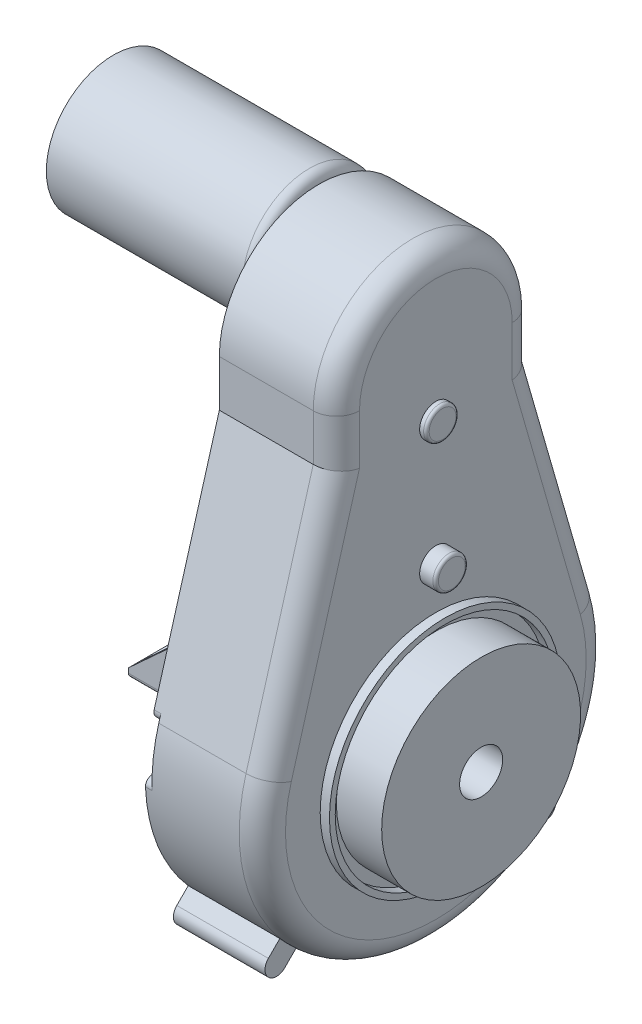
SolidWorks part; units mm, degrees
ref_plane "Front Plane" through (0, 0, 0) normal (0, 0, 1) x (1, 0, 0)
ref_plane "Top Plane" through (0, 0, 0) normal (0, 1, 0) x (1, 0, 0)
ref_plane "Right Plane" through (0, 0, 0) normal (1, 0, 0) x (0, 0, -1)
sketch "Sketch1" plane through (0, 0, 0) normal (1, 0, 0) x (0, 0, -1)
  line L0 (0, 0) -> (0, 90.17) construction
  line L1 (-27.305, 90.17) -> (-27.305, 77.4065)
  line L2 (-27.305, 77.4065) -> (-45.7719, 13.1557)
  line L3 (-45.7719, 13.1557) -> (45.7719, 13.1557) construction
  line L4 (45.7719, 13.1557) -> (27.305, 77.4065)
  line L5 (27.305, 77.4065) -> (27.305, 90.17)
  line L6 (-27.305, 90.17) -> (27.305, 90.17) construction
  line L7 (27.305, 77.4065) -> (-27.305, 77.4065) construction
  arc A0 (-27.305, 90.17) -> (27.305, 90.17) centre (0, 90.17) cw
  arc A1 (-45.7719, 13.1557) -> (45.7719, 13.1557) centre (0, 0) ccw
  dimension "D2" = 40.0685
  dimension "D3" = 165.1
  dimension "D4" = 47.625
  dimension "D1" = 54.61
extrude "Boss-Extrude1" add sketch "Sketch1" along normal blind 32.131
fillet "Fillet1" radius 6.35 6 edges at (32.131, 83.7883, -27.305) (32.131, 45.2811, -36.5385) (32.131, -47.625, 0) (32.131, 45.2811, 36.5385) (32.131, 83.7883, 27.305) (32.131, 117.475, 0)
sketch "Sketch2" plane through (0, 0, 0) normal (-1, 0, 0) x (0, 0, 1)
  line L0 (0, 0) -> (0, 90.17) construction
  line L1 (-22.5425, 90.17) -> (-22.5425, 77.4065)
  line L2 (-22.5425, 77.4065) -> (-41.2267, 11.7282)
  line L3 (-41.2267, 11.7282) -> (41.2267, 11.7282) construction
  line L4 (41.2267, 11.7282) -> (22.5425, 77.4065)
  line L5 (22.5425, 77.4065) -> (22.5425, 90.17)
  line L6 (-22.5425, 90.17) -> (22.5425, 90.17) construction
  line L7 (22.5425, 77.4065) -> (-22.5425, 77.4065) construction
  arc A0 (-22.5425, 90.17) -> (22.5425, 90.17) centre (0, 90.17) cw
  arc A1 (-41.2267, 11.7282) -> (41.2267, 11.7282) centre (0, 0) ccw
  dimension "D2" = 35.306
  dimension "D3" = 155.575
  dimension "D4" = 42.8625
  dimension "D1" = 45.085
extrude "Cut-Extrude1" cut sketch "Sketch2" against normal blind 1.8415
sketch "Sketch3" plane through (0, 0, 0) normal (-1, 0, 0) x (0, 0, 1)
  line L0 (0, 0) -> (0, 101.6) construction
  circle A0 centre (0, 101.6) radius 18.415
  dimension "D1" = 36.83
  dimension "D2" = 101.6
extrude "Boss-Extrude2" add sketch "Sketch3" along normal blind 56.388 separate body
fillet "Fillet2" radius 2.54 1 edges at (0, 101.6, 18.415)
sketch "Sketch4" plane through (32.131, 0, 0) normal (1, 0, 0) x (0, 0, -1)
  circle A0 centre (0, 0) radius 31.75
  circle A1 centre (0, 0) radius 30.1625
  dimension "D1" = 1.5875
  dimension "D2" = 63.5
extrude "Boss-Extrude3" add sketch "Sketch4" along normal blind 2.54
sketch "Sketch5" plane through (32.131, 0, 0) normal (1, 0, 0) x (0, 0, -1)
  circle A0 centre (0, 0) radius 27.305
  dimension "D1" = 54.61
extrude "Boss-Extrude4" add sketch "Sketch5" along normal blind 12.4333
sketch "Sketch6" plane through (0, 0, 0) normal (-1, 0, 0) x (0, 0, 1)
  line L0 (0, 0) -> (36.7441, -36.7441) construction
  line L1 (0, 0) -> (-36.7441, -36.7441) construction
  line L2 (0, 0) -> (0, 101.6) construction
  line L3 (34.4991, -38.9892) -> (31.356, -35.8461)
  line L4 (31.356, -35.8461) -> (35.8461, -31.356)
  line L5 (35.8461, -31.356) -> (38.9892, -34.4991)
  line L6 (-38.9892, -34.4991) -> (-35.8461, -31.356)
  line L7 (-35.8461, -31.356) -> (-31.356, -35.8461)
  line L8 (-31.356, -35.8461) -> (-34.4991, -38.9892)
  arc A0 (34.4991, -38.9892) -> (38.9892, -34.4991) centre (36.7441, -36.7441) ccw
  arc A1 (-45.7719, 13.1557) -> (45.7719, 13.1557) centre (0, 0) ccw construction
  arc A2 (-38.9892, -34.4991) -> (-34.4991, -38.9892) centre (-36.7441, -36.7441) ccw
  dimension "D4" = 7.62
  dimension "D5" = 7.62
  dimension "D1" = 135
  dimension "D2" = 90
  dimension "D3" = 6.35
  dimension "D6" = 6.35
extrude "Boss-Extrude5" add sketch "Sketch6" against normal blind 25.146
sketch "Sketch7" plane through (32.131, 0, 0) normal (1, 0, 0) x (0, 0, -1)
  line L0 (0, 0) -> (0, 77.47) construction
  circle A0 centre (0, 77.47) radius 4.445
  arc A2 (27.305, 90.17) -> (-27.305, 90.17) centre (0, 90.17) ccw construction
  dimension "D1" = 8.89
  dimension "D2" = 44.45
extrude "Boss-Extrude6" add sketch "Sketch7" along normal blind 1.8542 and the other way offset from surface (34.6837 mm away) 4.3942 other way up to face at (1.8415, 54.4269, 0)
sketch "Sketch8" plane through (32.131, 0, 0) normal (1, 0, 0) x (0, 0, -1)
  line L0 (0, 0) -> (0, 43.18) construction
  circle A0 centre (0, 43.18) radius 4.445
  circle A1 centre (0, 77.47) radius 4.445 construction
  dimension "D1" = 8.89
  dimension "D2" = 43.18
extrude "Boss-Extrude7" add sketch "Sketch8" along normal blind 4.3942 and the other way offset from surface (32.1437 mm away) 1.8542 other way up to face at (1.8415, 77.47, -4.445)
fillet "Fillet3" radius 0.762 4 edges at (36.5252, 43.18, -4.445) (33.9852, 77.47, -4.445) (-2.5527, 77.47, -4.445) (-0.0127, 43.18, -4.445)
sketch "Sketch9" plane through (1.8415, 0, 0) normal (-1, 0, 0) x (0, 0, 1)
  circle A0 centre (0, 0) radius 5.9055
  dimension "D1" = 11.811
extrude "Cut-Extrude2" cut sketch "Sketch9" against normal through all
sketch "Sketch10" plane through (1.8415, 0, 0) normal (-1, 0, 0) x (0, 0, 1)
  line L1 (-67.1064, 12.7) -> (67.1064, 12.7)
  line L2 (-67.1064, 12.7) -> (-67.1064, 0)
  line L3 (-67.1064, 0) -> (67.1064, 0)
  line L4 (67.1064, 12.7) -> (67.1064, 0)
  dimension "D1" = 12.7
extrude "Cut-Extrude3" cut sketch "Sketch10" along normal through all
fillet "Fillet4" radius 1.905 8 edges at (0.9207, 0, -42.8625) (0.9207, 0, 42.8625) (0.9207, 0, -47.625) (0.9207, 0, 47.625) (0.9207, 12.7, -45.9004) (0.9207, 12.7, 45.9004) (0.9207, 12.7, 40.9503) (0.9207, 12.7, -40.9503)
sketch "Sketch11" plane through (1.8415, 0, 0) normal (-1, 0, 0) x (0, 0, 1)
  line L0 (-38.862, 12.7) -> (-12.954, 12.7)
  line L1 (-12.954, 12.7) -> (-12.954, 29.21)
  line L2 (-12.954, 29.21) -> (-15.494, 29.21)
  line L3 (12.954, 29.21) -> (12.954, 12.7)
  line L4 (12.954, 12.7) -> (38.862, 12.7)
  line L5 (-12.954, 12.7) -> (12.954, 12.7) construction
  line L6 (0, 0) -> (0, 12.7) construction
  line L7 (-15.494, 29.21) -> (-15.494, 15.24)
  line L8 (-15.494, 15.24) -> (-24.638, 15.24)
  line L9 (-24.638, 15.24) -> (-24.638, 29.21)
  line L10 (-24.638, 29.21) -> (-27.178, 29.21)
  line L11 (-27.178, 29.21) -> (-27.178, 15.24)
  line L12 (-27.178, 15.24) -> (-36.322, 15.24)
  line L13 (-36.322, 15.24) -> (-36.322, 29.21)
  line L14 (-36.322, 29.21) -> (-38.862, 29.21)
  line L15 (-38.862, 29.21) -> (-38.862, 12.7)
  line L16 (12.954, 29.21) -> (15.494, 29.21)
  line L17 (15.494, 29.21) -> (15.494, 15.24)
  line L18 (15.494, 15.24) -> (24.638, 15.24)
  line L19 (24.638, 15.24) -> (24.638, 29.21)
  line L20 (24.638, 29.21) -> (27.178, 29.21)
  line L21 (27.178, 29.21) -> (27.178, 15.24)
  line L22 (27.178, 15.24) -> (36.322, 15.24)
  line L23 (36.322, 15.24) -> (36.322, 29.21)
  line L24 (36.322, 29.21) -> (38.862, 29.21)
  line L25 (38.862, 29.21) -> (38.862, 12.7)
  dimension "D1" = 25.908
  dimension "D2" = 25.908
  dimension "D3" = 25.908
  dimension "D4" = 2.54
  dimension "D5" = 2.54
  dimension "D6" = 16.51
  dimension "D7" = 12.7
  dimension "D8" = 2.54
  dimension "D9" = 16.51
  dimension "D10" = 2.54
extrude "Boss-Extrude8" add sketch "Sketch11" along normal blind 15.24
fillet "Fillet5" radius 1.27 12 edges at (-5.7785, 12.7, 12.954) (-5.7785, 15.24, 36.322) (-5.7785, 15.24, 24.638) (-5.7785, 12.7, 38.862) (-5.7785, 15.24, 27.178) (-5.7785, 15.24, 15.494) (-5.7785, 15.24, -24.638) (-5.7785, 15.24, -27.178) (-5.7785, 15.24, -36.322) (-5.7785, 15.24, -15.494) (-5.7785, 12.7, -12.954) (-5.7785, 12.7, -38.862)
sketch "Sketch12" plane through (0, 0, -38.862) normal (0, 0, -1) x (-1, 0, 0)
  line L0 (13.3985, 15.24) -> (-1.8415, 29.21)
  line L1 (13.3985, 29.21) -> (13.3985, 13.97) construction
  line L2 (-1.8415, 29.21) -> (13.3985, 29.21)
  line L3 (13.3985, 29.21) -> (13.3985, 15.24)
  line L4 (13.3985, 12.7) -> (-1.8415, 12.7) construction
  line L5 (-1.8415, 77.4065) -> (-1.8415, 28.9692) construction
  dimension "D1" = 2.54
extrude "Cut-Extrude4" cut sketch "Sketch12" against normal through all
sketch "Sketch13" plane through (0, 0, 0) normal (-1, 0, 0) x (0, 0, 1)
  line L0 (-36.2535, 29.21) -> (-38.862, 20.0406)
  line L1 (-38.862, 20.0406) -> (-38.862, 29.21)
  line L2 (-38.862, 29.21) -> (-36.2535, 29.21)
  line L3 (36.2535, 29.21) -> (38.862, 20.0406)
  line L4 (38.862, 20.0406) -> (38.862, 27.522)
  line L5 (38.862, 27.522) -> (41.6428, 27.522)
  line L6 (41.6428, 27.522) -> (41.1576, 29.21)
  line L7 (41.1576, 29.21) -> (36.2535, 29.21)
extrude "Boss-Extrude9" add sketch "Sketch13" against normal blind 6.35
